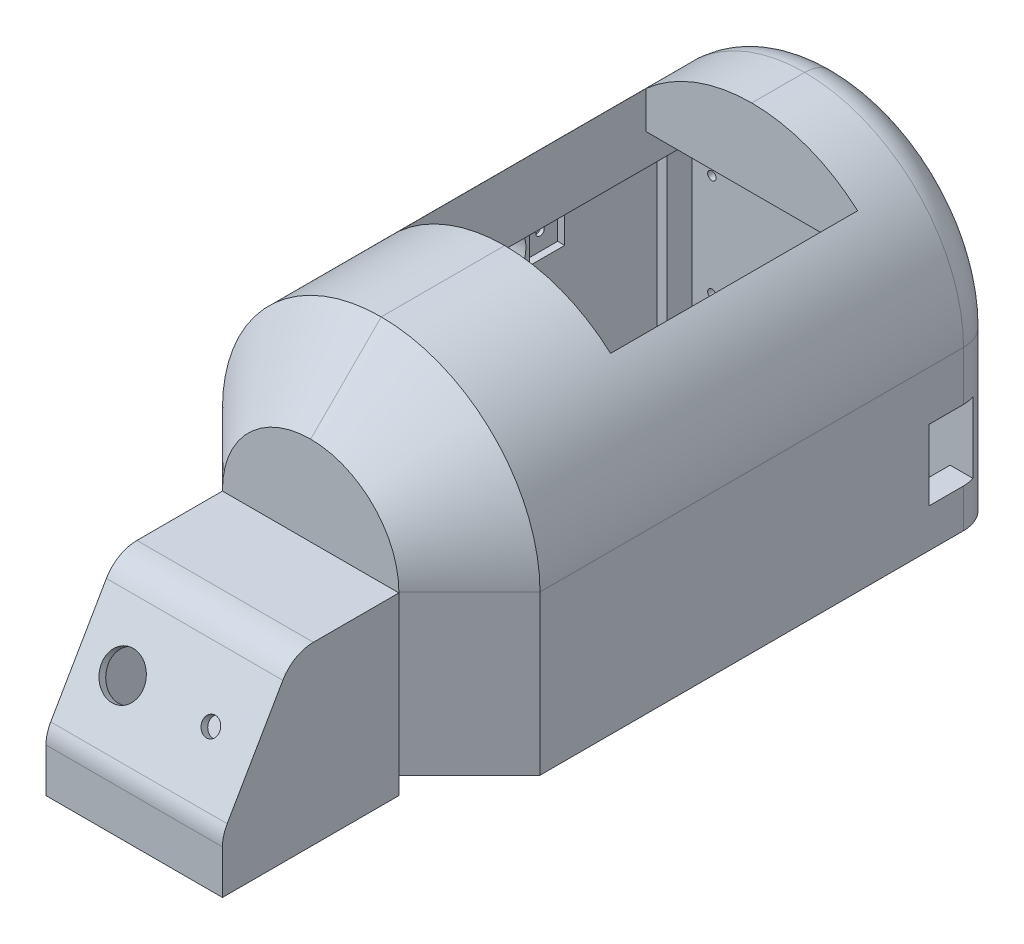
SolidWorks part; units mm, degrees
ref_plane "Piano frontale" through (0, 0, 0) normal (0, 0, 1) x (1, 0, 0)
ref_plane "Piano superiore" through (0, 0, 0) normal (0, 1, 0) x (1, 0, 0)
ref_plane "Piano destro" through (0, 0, 0) normal (1, 0, 0) x (0, 0, -1)
sketch "Schizzo1" plane through (0, 0, 0) normal (0, 1, 0) x (1, 0, 0)
  line L1 (-45, -75) -> (45, -75)
  line L2 (-45, -75) -> (-45, 75)
  line L3 (-45, 75) -> (45, 75)
  line L4 (45, -75) -> (45, 75)
  line L5 (-45, -75) -> (45, 75) construction
  line L6 (-45, 75) -> (45, -75) construction
  point P0 (0, 0)
  dimension "D1" = 90
  dimension "D2" = 150
extrude "Estrusione-Estrusione1" add sketch "Schizzo1" along normal blind 90
sketch "Schizzo4" plane through (0, 90, 0) normal (0, 1, 0) x (1, 0, 0)
  line L1 (-30, -20) -> (30, -20)
  line L2 (-30, -20) -> (-30, 50)
  line L3 (-30, 50) -> (30, 50)
  line L4 (30, -20) -> (30, 50)
  point P0 (0, 0)
  dimension "D1" = 60
  dimension "D2" = 70
  dimension "D3" = 50
extrude "Taglio-Estrusione2" cut sketch "Schizzo4" against normal blind 90
fillet "Raccordo5" radius 45 1 edges at (-45, 90, 0)
fillet "Raccordo6" radius 45 1 edges at (45, 90, 0)
chamfer "Smusso2" distance 20 angle 45 4 edges at (45, 22.5, 75) (31.8198, 76.8198, 75) (-45, 22.5, 75) (-31.8198, 76.8198, 75)
sketch "Schizzo7" plane through (0, 0, 75) normal (0, 0, 1) x (1, 0, 0)
  line L0 (25, 0) -> (25, 45) construction
  line L1 (-25, 0) -> (25, 0)
  line L2 (-25, 0) -> (-25, 44.7532)
  line L3 (-25, 44.7532) -> (25, 44.7532)
  line L4 (25, 0) -> (25, 44.7532)
extrude "Estrusione-Estrusione2" add sketch "Schizzo7" along normal blind 50
chamfer "Smusso3" distance 20 angle 60 1 edges at (0, 44.7532, 125) first distance on face at (0, 44.7532, 100)
fillet "Raccordo7" radius 10 1 edges at (0, 44.7532, 105)
fillet "Raccordo8" radius 10 1 edges at (0, 10.1122, 125)
sketch "Schizzo9" plane through (0, 0, 0) normal (0, -1, 0) x (1, 0, 0)
  line L0 (-25, 75) -> (25, 75)
  line L1 (25, 75) -> (25, 125)
  line L2 (25, 125) -> (-25, 125)
  line L3 (-25, 125) -> (-25, 75)
extrude "Estrusione-Estrusione3" add sketch "Schizzo9" along normal blind 5
fillet "Raccordo9" radius 10 4 edges at (-45, 22.5, -75) (45, 22.5, -75) (31.8198, 76.8198, -75) (-31.8198, 76.8198, -75)
sketch "Schizzo13" plane through (0, 0, 20) normal (0, 0, -1) x (-1, 0, 0)
  line L0 (30, 0) -> (-30, 0) construction
  line L1 (-22.5, 0) -> (22.5, 0)
  line L2 (-22.5, 0) -> (-22.5, 38.416)
  line L3 (-22.5, 38.416) -> (22.5, 38.416)
  line L4 (22.5, 0) -> (22.5, 38.416)
  line L5 (-30, 0) -> (-30, 78.541) construction
  line L6 (30, 0) -> (30, 78.541) construction
  dimension "D1" = 7.5
  dimension "D2" = 7.5
extrude "Taglio-Estrusione3" cut sketch "Schizzo13" against normal blind 79.9783
sketch "Schizzo14" plane through (30, 0, 0) normal (-1, 0, 0) x (0, 0, 1)
  line L0 (-15, 78.541) -> (-15, 0) construction
  line L1 (20, 78.541) -> (-50, 78.541) construction
  line L2 (20, 0) -> (-50, 0) construction
  line L4 (-61.2099, 0) -> (56.6346, 0)
  line L5 (-61.2099, 0) -> (-61.2099, 59.041)
  line L6 (-61.2099, 59.041) -> (56.6346, 59.041)
  line L7 (56.6346, 0) -> (56.6346, 59.041)
extrude "Taglio-Estrusione4" cut sketch "Schizzo14" against normal blind 8
ref_axis "Assi1" through (0, 90, -65) along (0, 0, 1)
ref_axis "Assi2" through (25, 44.7532, 75) along (-1, 0, 0)
ref_plane "Piano1" through (0, 0, 0) normal (1, 0, 0) x (0, 0, -1)
mirror "Specchia1" about plane through (0, 0, 0) normal (1, 0, 0) of "Taglio-Estrusione4"
sketch "Schizzo16" plane through (0, 59.041, 0) normal (0, -1, 0) x (1, 0, 0)
  line L0 (30, -15) -> (38, -15) construction
  line L1 (30, 20) -> (30, -50) construction
  line L2 (38, 56.6346) -> (38, -61.2099) construction
  line L3 (34, -61.2099) -> (34, 49.6139) construction
  line L4 (38, -61.2099) -> (30, -61.2099) construction
  line L6 (30, -25) -> (34, -25)
  line L7 (30, -25) -> (30, -5)
  line L8 (30, -5) -> (34, -5)
  line L9 (34, -25) -> (34, -5)
  point P10 (34, -15)
  dimension "D1" = 20
sketch "Schizzo18" plane through (30, 0, 0) normal (-1, 0, 0) x (0, 0, 1)
  circle A0 centre (-15, 48.541) radius 5
  dimension "D1" = 10
extrude "Taglio-Estrusione5" cut sketch "Schizzo18" against normal blind 9
extrude "Taglio-Estrusione7" cut sketch "Schizzo16" against normal blind 2 contours L9 L8 L7 L6
sketch "Schizzo23" plane through (0, 0, 0) normal (0, -1, 0) x (1, 0, 0)
  line L1 (-38, -61.2099) -> (38, -61.2099)
  line L2 (-38, -61.2099) -> (-38, 56.6346)
  line L3 (-38, 56.6346) -> (38, 56.6346)
  line L4 (38, -61.2099) -> (38, 56.6346)
extrude "Taglio-Estrusione8" cut sketch "Schizzo23" against normal blind 38
hole_wizard "Foro per Vite M2-2" positions "Schizzo24" profile "Schizzo25" hole size "M2" standard "ISO"
sketch "Schizzo24" plane through (0, 0, 0) normal (0, -1, 0) x (-1, 0, 0)
  line L0 (0, 75) -> (0, -75) construction
  line L1 (-35, 75) -> (35, 75) construction
  line L2 (22.5, -75) -> (-22.5, -75) construction
  line L4 (0, 0) -> (53.8934, 0) construction
  line L5 (25, -75) -> (45, -55) construction
  line L6 (45, 65) -> (45, -55) construction
  line L8 (-45, -55) -> (-25, -75) construction
  line L9 (-45, -55) -> (-45, 65) construction
  point P0 (40, 67)
  point P2 (30, -61.5147)
  point P4 (-30, -61.5147)
  point P19 (-40, 67)
  point P33 (-41.5, 5)
  point P35 (41.5, 5)
  dimension "D1" = 40
  dimension "D2" = 40
  dimension "D3" = 8
  dimension "D4" = 8
  dimension "D5" = 6
  dimension "D6" = 15
  dimension "D7" = 6
  dimension "D8" = 15
  dimension "D9" = 3.5
  dimension "D10" = 3.5
  dimension "D11" = 70
  dimension "D12" = 70
sketch "Schizzo25" plane through (-40, 0, -67) normal (1, 0, 0) x (0, 0, -1)
  line L0 (0, 0) -> (0, 4)
  line L1 (0, 4) -> (1.2, 4)
  line L2 (1.2, 4) -> (1.2, 0)
  line L5 (1.2, 0) -> (0, 0)
  line L10 (0, 4) -> (-1.2, 4) construction
  line L11 (0, -6.35) -> (0, 107.95) construction
  dimension "Hole Dia." = 2.4
  dimension "Hole Depth" = 4
  dimension "Drill Angle" = 180
hole_wizard "Foro per Vite M4-1" positions "Schizzo3D1" profile "Schizzo26" hole size "M4" standard "ISO"
sketch3d "Schizzo3D1"
  line L0 (-25, -5, 125) -> (-25, -5, 75) construction
  line L3 (-22.5, 0, 99.9783) -> (-22.5, -16.7046, 99.9783) construction
  line L5 (-22.5, 0, 99.9783) -> (18.7748, 0, 99.9783) construction
  line L6 (22.5, 0, 99.9783) -> (-22.5, 0, 99.9783) construction
  point P0 (0, -5, 84.7796)
  dimension "D1" = 25
  dimension "D2" = 16
sketch "Schizzo26" plane through (0, -5, 84.7796) normal (1, 0, 0) x (0, 0, -1)
  line L0 (0, 0) -> (0, 10)
  line L1 (0, 10) -> (2.25, 10)
  line L2 (2.25, 10) -> (2.25, 0)
  line L5 (2.25, 0) -> (0, 0)
  line L10 (0, 10) -> (-2.25, 10) construction
  line L11 (0, -6.35) -> (0, 107.95) construction
  dimension "Hole Dia." = 4.5
  dimension "Hole Depth" = 10
  dimension "Drill Angle" = 180
sketch "Schizzo29" plane through (0, 38, 0) normal (0, -1, 0) x (1, 0, 0)
  line L1 (-30, -50) -> (30, -50)
  line L2 (-30, -50) -> (-30, -61.2099)
  line L3 (-30, -61.2099) -> (30, -61.2099)
  line L4 (30, -50) -> (30, -61.2099)
extrude "Taglio-Estrusione9" cut sketch "Schizzo29" against normal blind 30
sketch "Schizzo30" plane through (0, 0, -61.2099) normal (0, 0, 1) x (1, 0, 0)
  line L0 (38, 55.7788) -> (-32, 55.7788)
  line L1 (38, 59.041) -> (38, 0) construction
  line L2 (-32, 55.7788) -> (-32, 3.7788)
  line L3 (-32, 3.7788) -> (38, 3.7788)
  line L4 (38, 3.7788) -> (38, 55.7788)
  dimension "D1" = 70
  dimension "D2" = 52
extrude "Taglio-Estrusione10" cut sketch "Schizzo30" against normal blind 7
hole_wizard "Foro per Vite M2-3" positions "Schizzo31" profile "Schizzo32" hole size "M2" standard "ISO"
sketch "Schizzo31" plane through (0, 0, -68.2099) normal (0, 0, 1) x (1, 0, 0)
  point P0 (-29.5, 48.2788)
  point P2 (-29.5, 19.2788)
  point P4 (22.5, 6.2788)
  point P6 (22.5, 53.2788)
sketch "Schizzo32" plane through (-29.5, 48.2788, -68.2099) normal (1, 0, 0) x (0, -1, 0)
  line L0 (0, 0) -> (0, 4.721)
  line L1 (0, 4.721) -> (1.2, 4)
  line L2 (1.2, 4) -> (1.2, 0)
  line L5 (1.2, 0) -> (0, 0)
  line L10 (0, 4.721) -> (-1.2, 4) construction
  line L11 (0, -6.35) -> (0, 107.95) construction
  dimension "Hole Dia." = 2.4
  dimension "Hole Depth" = 4
  dimension "Drill Angle" = 118
sketch "Schizzo33" plane through (38, 0, 0) normal (-1, 0, 0) x (0, 0, 1)
  line L0 (-68.2099, 3.7788) -> (-68.2099, 55.7788) construction
  line L1 (-68.2099, 11) -> (-55.2099, 11)
  line L2 (-68.2099, 11) -> (-68.2099, 31)
  line L3 (-68.2099, 31) -> (-55.2099, 31)
  line L4 (-55.2099, 11) -> (-55.2099, 31)
  line L6 (55, 0) -> (-65, 0) construction
  dimension "D1" = 20
  dimension "D2" = 13
  dimension "D3" = 11
extrude "Taglio-Estrusione11" cut sketch "Schizzo33" against normal blind 36 contours L4 L3 L2 L1
sketch "Schizzo36" plane through (0, 56.6546, 98.1287) normal (0, 0.5, 0.866) x (1, 0, 0)
  line L0 (0, -19.5161) -> (0, -51.0631) construction
  line L1 (25, -19.5161) -> (-25, -19.5161) construction
  line L2 (-25, -51.0631) -> (25, -51.0631) construction
  line L3 (-25, -35.2896) -> (25, -35.2896) construction
  line L4 (-25, -51.0631) -> (-25, -19.5161) construction
  line L5 (25, -19.5161) -> (25, -51.0631) construction
  line L7 (-23.0399, -21.1584) -> (23.0399, -21.1584)
  line L8 (-23.0399, -21.1584) -> (-23.0399, -49.4209)
  line L9 (-23.0399, -49.4209) -> (23.0399, -49.4209)
  line L10 (23.0399, -21.1584) -> (23.0399, -49.4209)
  line L11 (-23.0399, -21.1584) -> (23.0399, -49.4209) construction
  line L12 (-23.0399, -49.4209) -> (23.0399, -21.1584) construction
  point P12 (0, -35.2896)
extrude "Taglio-Estrusione12" cut sketch "Schizzo36" against normal blind 28
sketch "Schizzo37" plane through (23.0399, 0, 0) normal (-1, 0, 0) x (0, 0, 1)
  line L0 (122.8391, 13.8549) -> (108.7079, 38.331)
  line L1 (108.7079, 38.331) -> (106.8091, 37.2347)
  line L2 (84.4592, 24.331) -> (108.7079, 38.331) construction
  line L3 (106.8091, 37.2347) -> (120.9403, 12.7587)
  line L4 (98.5904, -0.1451) -> (122.8391, 13.8549) construction
  line L5 (120.9403, 12.7587) -> (122.8391, 13.8549)
extrude "Estrusione-Estrusione4" add sketch "Schizzo37" along normal up to next
sketch "Schizzo38" plane through (0, 56.6546, 98.1287) normal (0, 0.5, 0.866) x (1, 0, 0)
  line L0 (0, -19.5161) -> (0, -51.0631) construction
  line L3 (25, -19.5161) -> (-25, -19.5161) construction
  line L6 (-25, -51.0631) -> (25, -51.0631) construction
  line L7 (-25, -35.2896) -> (25, -35.2896) construction
  line L8 (-25, -51.0631) -> (-25, -19.5161) construction
  line L9 (25, -19.5161) -> (25, -51.0631) construction
  circle A0 centre (-12.5, -35.2896) radius 6
  circle A1 centre (12.5, -35.2896) radius 2.5
  dimension "D1" = 12
  dimension "D2" = 5
  dimension "D3" = 12.5
extrude "Taglio-Estrusione13" cut sketch "Schizzo38" against normal blind 28
ref_axis "Assi3" through (107.2361, 48.541, -15) along (-1, 0, 0)
sketch "Schizzo39" plane through (-38, 0, 0) normal (1, 0, 0) x (0, 0, -1)
  line L0 (15, 57.9632) -> (15, 37.1322) construction
  line L2 (-5, 53.541) -> (5, 53.541)
  line L3 (-5, 53.541) -> (-5, 43.541)
  line L4 (-5, 43.541) -> (5, 43.541)
  line L5 (5, 53.541) -> (5, 43.541)
  line L6 (-5, 53.541) -> (5, 43.541) construction
  line L7 (-5, 43.541) -> (5, 53.541) construction
  line L8 (25, 53.541) -> (35, 53.541)
  line L9 (25, 53.541) -> (25, 43.541)
  line L10 (25, 43.541) -> (35, 43.541)
  line L11 (35, 53.541) -> (35, 43.541)
  line L12 (25, 53.541) -> (35, 43.541) construction
  line L13 (25, 43.541) -> (35, 53.541) construction
  circle A0 centre (15, 48.541) radius 9
  point P0 (15, 48.541)
  point P6 (0, 48.541)
  point P11 (30, 48.541)
  point P17 (0, 48.541)
  dimension "D1" = 18
  dimension "D2" = 15
  dimension "D3" = 10
  dimension "D4" = 10
  dimension "D5" = 10
  dimension "D6" = 10
extrude "Taglio-Estrusione14" cut sketch "Schizzo39" against normal blind 2
sketch "Schizzo40" plane through (-45, 0, 0) normal (-1, 0, 0) x (0, 0, 1)
  line L0 (-65, 0) -> (55, 0) construction
  line L1 (22, 15) -> (54, 15)
  line L2 (22, 15) -> (22, 5)
  line L3 (22, 5) -> (54, 5)
  line L4 (54, 15) -> (54, 5)
  line L5 (22, 15) -> (54, 5) construction
  line L6 (22, 5) -> (54, 15) construction
  line L7 (55, 0) -> (55, 45) construction
  point P0 (38, 10)
  dimension "D1" = 5
  dimension "D2" = 10
  dimension "D3" = 32
  dimension "D4" = 1
extrude "Taglio-Estrusione15" cut sketch "Schizzo40" against normal blind 10 contours L3 L4 L1 L2
sketch "Schizzo42" plane through (-45, 0, 0) normal (-1, 0, 0) x (0, 0, 1)
  circle A0 centre (-30, 48.541) radius 4
  circle A1 centre (0, 48.541) radius 4
  point P0 (-15, 48.541)
  dimension "D3" = 8
  dimension "D4" = 8
  dimension "D1" = 15
  dimension "D2" = 15
extrude "Taglio-Estrusione16" cut sketch "Schizzo42" against normal blind 3 contours A1 | A0
hole_wizard "Foro svasato per Vite M2-3" positions "Schizzo47" profile "Schizzo48" countersink size "M2" standard "ISO"
sketch "Schizzo47" plane through (-42, 0, 0) normal (-1, 0, 0) x (0, 0, 1)
  point P0 (-30, 48.541)
  point P3 (0, 48.541)
sketch "Schizzo48" plane through (-42, 48.541, -30) normal (0, 1, 0) x (0, 0, 1)
  line L0 (0, 0) -> (0, 6.721)
  line L1 (0, 6.721) -> (1.2, 6)
  line L2 (1.2, 6) -> (1.2, 1)
  line L3 (1.2, 1) -> (2.2, 0)
  line L5 (2.2, 0) -> (0, 0)
  line L6 (-1.2, 1) -> (-2.2, 0) construction
  line L10 (0, 6.721) -> (-1.2, 6) construction
  line L11 (0, -6.35) -> (0, 107.95) construction
  dimension "Hole Dia." = 2.4
  dimension "Hole Depth" = 6
  dimension "Near C'Sink Dia." = 4.4
  dimension "Near C'Sink Angle" = 90
  dimension "Drill Angle" = 118
sketch "Schizzo50" plane through (0, 0, -61.2099) normal (0, 0, 1) x (1, 0, 0)
  line L0 (38, 59.041) -> (38, 55.7788)
  line L1 (38, 55.7788) -> (-32, 55.7788)
  line L2 (-32, 55.7788) -> (-32, 3.7788)
  line L3 (-32, 3.7788) -> (-35.1813, 3.7788)
  line L4 (-35.1813, 3.7788) -> (-35.1813, 59.041)
  line L5 (-38, 59.041) -> (-30, 59.041) construction
  line L6 (-35.1813, 59.041) -> (38, 59.041)
extrude "Taglio-Estrusione18" cut sketch "Schizzo50" against normal blind 7
sketch "Schizzo53" plane through (-40, 0, 0) normal (1, 0, 0) x (0, 0, -1)
  circle A0 centre (15, 48.541) radius 9
  point P0 (15, 48.541)
extrude "Taglio-Estrusione19" cut sketch "Schizzo53" against normal blind 2.75
sketch "Schizzo54" plane through (0, 38, 0) normal (0, -1, 0) x (1, 0, 0)
  line L1 (30, 20) -> (-30, 20)
  line L2 (30, 20) -> (30, 56.6346)
  line L3 (30, 56.6346) -> (-30, 56.6346)
  line L4 (-30, 20) -> (-30, 56.6346)
extrude "Taglio-Estrusione20" cut sketch "Schizzo54" against normal blind 24.75
